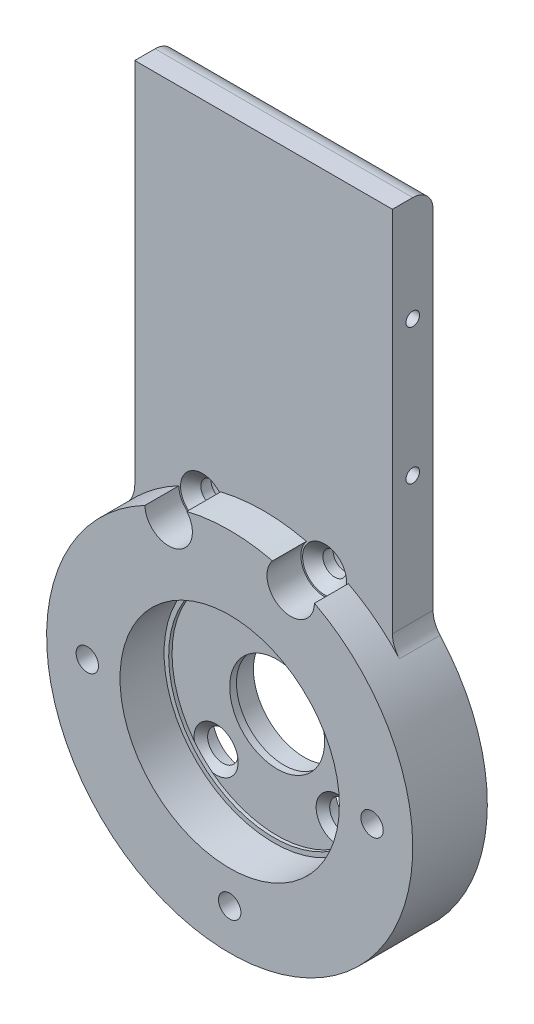
SolidWorks part; units mm, degrees
ref_plane "Спереди" through (0, 0, 0) normal (0, 0, 1) x (1, 0, 0)
ref_plane "Сверху" through (0, 0, 0) normal (0, 1, 0) x (1, 0, 0)
ref_plane "Справа" through (0, 0, 0) normal (1, 0, 0) x (0, 0, -1)
sketch "Эскиз1" plane through (0, 0, 0) normal (0, 0, 1) x (1, 0, 0)
  line L0 (0, 75) -> (0, -19) construction
  line L1 (-19, 75) -> (19, 75)
  line L2 (-19, 75) -> (-19, -19)
  line L3 (-19, -19) -> (19, -19)
  line L4 (19, 75) -> (19, -19)
  line L5 (-19, 0) -> (19, 0) construction
  dimension "D1" = 38
  dimension "D2" = 19
  dimension "D3" = 75
extrude "тело" add sketch "Эскиз1" along normal blind 6
sketch "Эскиз5" plane through (0, 0, 6) normal (0, 0, 1) x (1, 0, 0)
  circle A0 centre (0, 0) radius 5
  dimension "D1" = 10
extrude "ось двигателя1" cut sketch "Эскиз5" against normal through all and the other way through all
sketch "Эскиз8" plane through (0, 0, 6) normal (0, 0, 1) x (1, 0, 0)
  line L8 (-19, 0) -> (19, 0) construction
  circle A1 centre (0, 0) radius 27
  point P15 (0, 0)
  dimension "D1" = 54
extrude "выступ подшипника" add sketch "Эскиз8" along normal blind 5 and the other way up to surface (6 mm away) other way up to face at (5, 0, 0)
sketch "Эскиз6" plane through (0, 0, 0) normal (0, 0, -1) x (-1, 0, 0)
  line L0 (0, 75) -> (0, 0) construction
  line L1 (-9, 24) -> (9, 24) construction
  line L2 (-9, 24) -> (-9, -9) construction
  line L3 (-9, -9) -> (9, -9) construction
  line L4 (9, 24) -> (9, -9) construction
  line L7 (-9, 7.5) -> (9, 7.5) construction
  line L8 (-19, 75) -> (19, 75) construction
  circle A0 centre (-9, 24) radius 1.75
  circle A1 centre (9, 24) radius 1.75
  circle A2 centre (9, -9) radius 1.75
  circle A3 centre (-9, -9) radius 1.75
  dimension "D1" = 3.5
  dimension "D2" = 18
  dimension "D3" = 33
  dimension "D4" = 9
extrude "крепления к двигателю" cut sketch "Эскиз6" against normal through all
sketch "Эскиз16" plane through (0, 0, 11) normal (0, 0, 1) x (1, 0, 0)
  circle A0 centre (0, 0) radius 16.175
  dimension "D1" = 32.35
extrude "углубление подшипника" cut sketch "Эскиз16" against normal blind 7
sketch "Эскиз7" plane through (0, 0, 0) normal (0, 0, -1) x (-1, 0, 0)
  line L0 (0, 75) -> (0, 0) construction
  line L3 (-5, 16.5) -> (5, 16.5)
  line L4 (-5, 9.5) -> (5, 9.5)
  line L5 (-8.5, 13) -> (8.5, 13) construction
  line L7 (-9, 24) -> (9, 24) construction
  line L8 (-9, 24) -> (-9, -9) construction
  line L9 (-9, -9) -> (9, -9) construction
  line L10 (9, 24) -> (9, -9) construction
  line L11 (-19, 75) -> (19, 75) construction
  circle A0 centre (-9, 24) radius 4.5
  circle A1 centre (9, 24) radius 4.5
  circle A2 centre (-9, -9) radius 4.5
  circle A3 centre (9, -9) radius 4.5
  circle A4 centre (0, 0) radius 7.5
  arc A5 (-5, 16.5) -> (-5, 9.5) centre (-5, 13) ccw
  arc A6 (5, 9.5) -> (5, 16.5) centre (5, 13) ccw
  point P8 (0, 13)
  point P11 (0, 0)
  point P14 (0, -1.1885)
  point P17 (0, 0)
  point P22 (-8.5, 13)
  point P24 (8.5, 13)
  dimension "D1" = 9
  dimension "D2" = 15
  dimension "D3" = 17
  dimension "D4" = 7
  dimension "D5" = 13
  dimension "D6" = 18
  dimension "D7" = 33
extrude "выступы двигателя" cut sketch "Эскиз7" against normal blind 3
sketch "Эскиз10" plane through (0, 0, 11) normal (0, 0, 1) x (1, 0, 0)
  circle A0 centre (-9, 24) radius 3.5
  circle A1 centre (9, 24) radius 3.5
  dimension "D1" = 7
extrude "вырез под шляпки болтов" cut sketch "Эскиз10" against normal up to surface (5 mm away) up to face at (0, 36.5398, 6)
sketch "Эскиз11" plane through (0, 0, 11) normal (0, 0, 1) x (1, 0, 0)
  circle A0 centre (0, 0) radius 21 construction
  circle A1 centre (21, 0) radius 1.65
  circle A2 centre (-21, 0) radius 1.65
  circle A3 centre (0, -21) radius 1.65
  circle A5 centre (0, 0) radius 7.5 construction
  dimension "D1" = 42
  dimension "D2" = 3.3
extrude "крепление стакана" cut sketch "Эскиз11" against normal through all
sketch "Эскиз12" plane through (0, 0, 0) normal (0, 0, -1) x (-1, 0, 0)
  line L1 (-18.1, 1.6743) -> (-21, 3.3486)
  line L2 (-21, 3.3486) -> (-23.9, 1.6743)
  line L3 (-23.9, 1.6743) -> (-23.9, -1.6743)
  line L4 (-23.9, -1.6743) -> (-21, -3.3486)
  line L5 (-21, -3.3486) -> (-18.1, -1.6743)
  line L6 (-18.1, -1.6743) -> (-18.1, 1.6743)
  line L7 (2.9, -19.3257) -> (0, -17.6514)
  line L8 (0, -17.6514) -> (-2.9, -19.3257)
  line L9 (-2.9, -19.3257) -> (-2.9, -22.6743)
  line L10 (-2.9, -22.6743) -> (0, -24.3486)
  line L11 (0, -24.3486) -> (2.9, -22.6743)
  line L12 (2.9, -22.6743) -> (2.9, -19.3257)
  line L13 (23.9, 1.6743) -> (21, 3.3486)
  line L14 (21, 3.3486) -> (18.1, 1.6743)
  line L15 (18.1, 1.6743) -> (18.1, -1.6743)
  line L16 (18.1, -1.6743) -> (21, -3.3486)
  line L17 (21, -3.3486) -> (23.9, -1.6743)
  line L18 (23.9, -1.6743) -> (23.9, 1.6743)
  circle A0 centre (-21, 0) radius 2.9 construction
  circle A1 centre (0, -21) radius 2.9 construction
  circle A2 centre (21, 0) radius 2.9 construction
  dimension "D1" = 5.8
extrude "Вырез-Вытянуть3" cut sketch "Эскиз12" against normal blind 5
chamfer "Фаска1" distance 1.5 angle 45 4 edges at (-7.25, 24, 6) (10.75, -9, 4) (-7.25, -9, 4) (10.75, 24, 6)
fillet "Скругление5" radius 4 2 edges at (19, 19.1833, 3) (-19, 19.1833, 3)
sketch "Эскиз17" plane through (0, 0, 4) normal (0, 0, 1) x (1, 0, 0)
  circle A0 centre (0, 0) radius 7
  dimension "D1" = 14
extrude "сквозное отверстие" cut sketch "Эскиз17" against normal through all
sketch "Эскиз18" plane through (0, 0, 4) normal (0, 0, 1) x (1, 0, 0)
  circle A0 centre (0, 0) radius 16.175
  circle A1 centre (0, 0) radius 15.5
  dimension "D2" = 31
extrude "уступ" add sketch "Эскиз18" along normal blind 0.5
sketch "Эскиз19" plane through (19, 0, 0) normal (1, 0, 0) x (0, 0, -1)
  line L0 (-3, 75) -> (-3, 20.7846) construction
  line L3 (-6, 75) -> (0, 75) construction
  line L4 (-6, 20.7846) -> (0, 20.7846) construction
  line L5 (-6, 69.5) -> (0, 69.5) construction
  line L6 (-6, 20.7846) -> (-6, 75) construction
  line L7 (0, 20.7846) -> (0, 75) construction
  circle A0 centre (-3, 59.5) radius 1
  circle A1 centre (-3, 39.5) radius 1
  dimension "D2" = 2
  dimension "D1" = 5.5
  dimension "D3" = 10
  dimension "D4" = 20
extrude "отверстия под шурупы" cut sketch "Эскиз19" against normal through all
fillet "Скругление6" radius 3 1 edges at (0, 75, 0)
